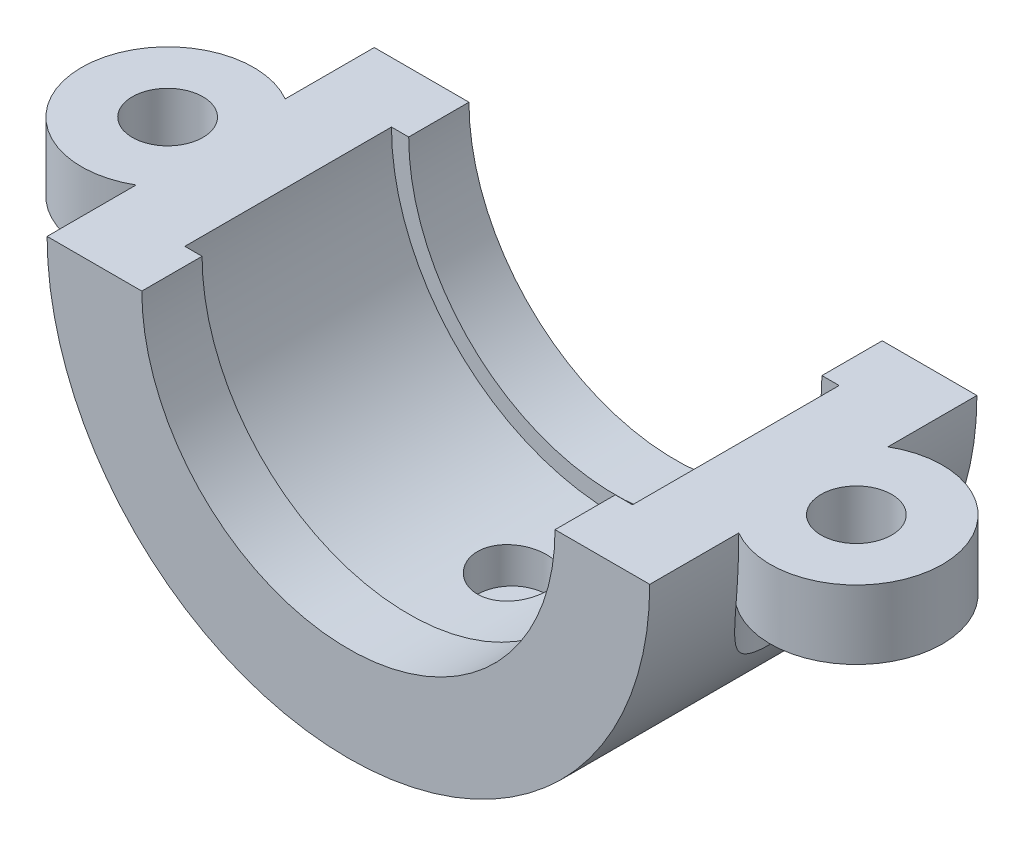
SolidWorks part; units mm, degrees
material "Сталь"
ref_plane "Спереди" through (0, 0, 0) normal (0, 0, 1) x (1, 0, 0)
ref_plane "Сверху" through (0, 0, 0) normal (0, 1, 0) x (1, 0, 0)
ref_plane "Справа" through (0, 0, 0) normal (1, 0, 0) x (0, 0, -1)
sketch "Эскиз1" plane through (0, 0, 0) normal (0, 0, 1) x (1, 0, 0)
  line L0 (-35, 0) -> (35, 0)
  circle A0 centre (0, 0) radius 24
  circle A1 centre (0, 0) radius 35
  circle A2 centre (0, 0) radius 26
  dimension "D1" = 48
  dimension "D2" = 70
  dimension "D3" = 52
extrude "Бобышка-Вытянуть2" add sketch "Эскиз1" along normal mid plane 38 contours A2 L0 A1 | L0 A2 A0 region at (25, -0.5814, 0) region at (30.5, -0.7826, 0)
sketch "Эскиз2" plane through (0, 0, 0) normal (0, 1, 0) x (1, 0, 0)
  circle A0 centre (40, 0) radius 10
  dimension "D1" = 20
  dimension "D2" = 40
extrude "Бобышка-Вытянуть3" add sketch "Эскиз2" against normal blind 40
sketch "Эскиз3" plane through (0, -40, 0) normal (0, -1, 0) x (1, 0, 0)
  circle A1 centre (40, 0) radius 10
  circle A2 centre (40, 0) radius 10
  dimension "D1" = 0
extrude "Вырез-Вытянуть1" cut sketch "Эскиз3" against normal offset from surface (32 mm away) 8 up to face at (-29.5, 0, 0)
sketch "Эскиз4" plane through (0, -8, 0) normal (0, -1, 0) x (1, 0, 0)
  circle A0 centre (40, 0) radius 4.1
  dimension "D1" = 8.2
extrude "Вырез-Вытянуть2" cut sketch "Эскиз4" against normal through all
mirror "Зеркальное отражение1" about plane through (0, 0, 0) normal (1, 0, 0) of "Вырез-Вытянуть2", "Вырез-Вытянуть1", "Бобышка-Вытянуть3"
sketch "Эскиз5" plane through (0, 0, 0) normal (0, 1, 0) x (1, 0, 0)
  circle A0 centre (0, 0) radius 10
  circle A1 centre (0, 0) radius 1.5
  dimension "D1" = 20
  dimension "D2" = 3
extrude "Бобышка-Вытянуть4" add sketch "Эскиз5" along normal up to surface (2 mm away) from offset 37 contours A0 A1 | A1 region at (-9.7172, 0, 0) region at (0, 0, 0) up to face at (0, -10.1654, -0.2093) offset against normal yes
extrude "Вырез-Вытянуть3" cut sketch "Эскиз5<4>" against normal through all contours A1 region at (0, 0, 0)
sketch "Эскиз5<4>" plane through (0, 0, 0) normal (0, 1, 0) x (1, 0, 0) same geometry as "Эскиз5"
extrude "Вырез-Вытянуть4" cut sketch "Эскиз1<4>" against normal mid plane 24 contours L0 A2 A0 region at (25, -0.5814, 0)
sketch "Эскиз1<4>" plane through (0, 0, 0) normal (0, 0, 1) x (1, 0, 0) same geometry as "Эскиз1"
sketch "Эскиз6" plane through (0, 0, 0) normal (0, 1, 0) x (1, 0, 0)
  circle A0 centre (0, 0) radius 4
  dimension "D1" = 8
extrude "Вырез-Вытянуть5" cut sketch "Эскиз6" against normal blind 30
